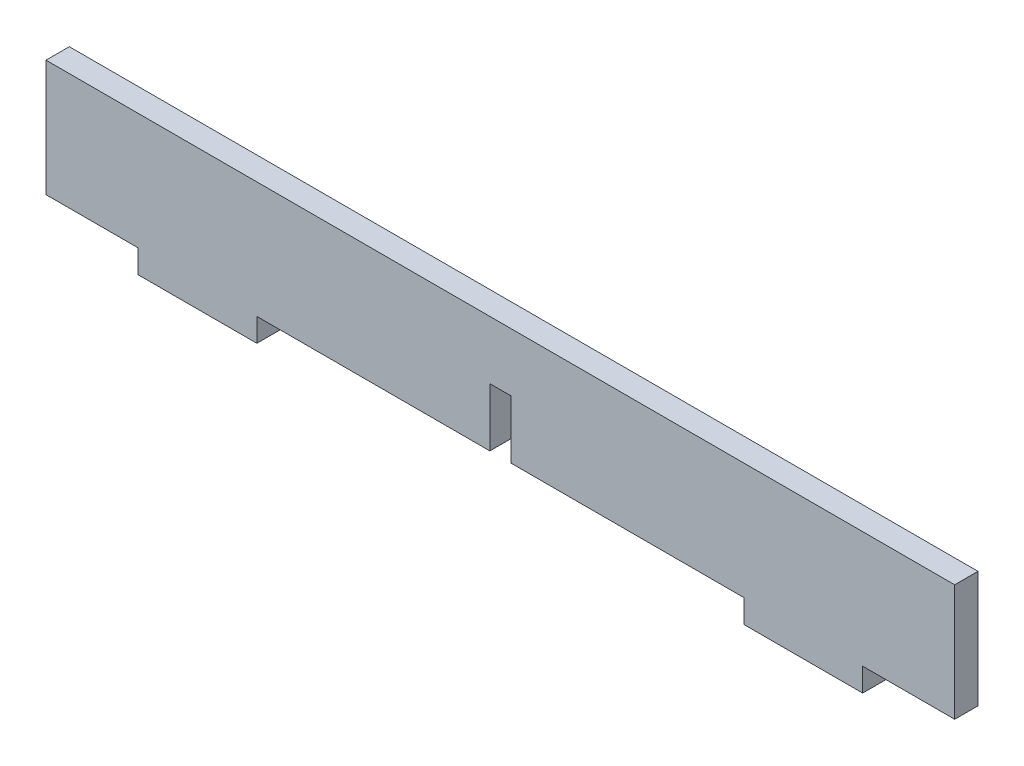
SolidWorks part; units mm, degrees
ref_plane "前基準面" through (0, 0, 0) normal (0, 0, 1) x (1, 0, 0)
ref_plane "上基準面" through (0, 0, 0) normal (0, 1, 0) x (1, 0, 0)
ref_plane "右基準面" through (0, 0, 0) normal (1, 0, 0) x (0, 0, -1)
sketch "草圖1" plane through (0, 0, 0) normal (0, 0, 1) x (1, 0, 0)
  line L0 (0, 0) -> (0, 24.9222) construction
  line L1 (-39, 2) -> (-31.1, 2)
  line L2 (-39, 2) -> (-39, 12)
  line L3 (-39, 12) -> (39, 12)
  line L4 (39, 2) -> (39, 12)
  line L5 (0.9, 2) -> (20.9, 2)
  line L6 (31.1, 2) -> (31.1, 0)
  line L7 (31.1, 0) -> (20.9, 0)
  line L8 (20.9, 2) -> (20.9, 0)
  line L9 (31.1, 2) -> (39, 2)
  line L10 (-20.9, 2) -> (-20.9, 0)
  line L11 (-20.9, 0) -> (-31.1, 0)
  line L12 (-31.1, 2) -> (-31.1, 0)
  line L13 (-11.3843, 0) -> (12.3473, 0) construction
  line L14 (-20.9, 2) -> (-0.9, 2)
  line L15 (-26, 0) -> (-26, 12) construction
  line L16 (-0.9, 2) -> (-0.9, 7)
  line L17 (-0.9, 7) -> (0.9, 7)
  line L18 (0.9, 2) -> (0.9, 7)
  dimension "D1" = 10
  dimension "D2" = 10.2
  dimension "D3" = 26
  dimension "D4" = 2
  dimension "D5" = 78
  dimension "D6" = 1.8
  dimension "D7" = 5
extrude "填料-伸長1" add sketch "草圖1" along normal blind 2
